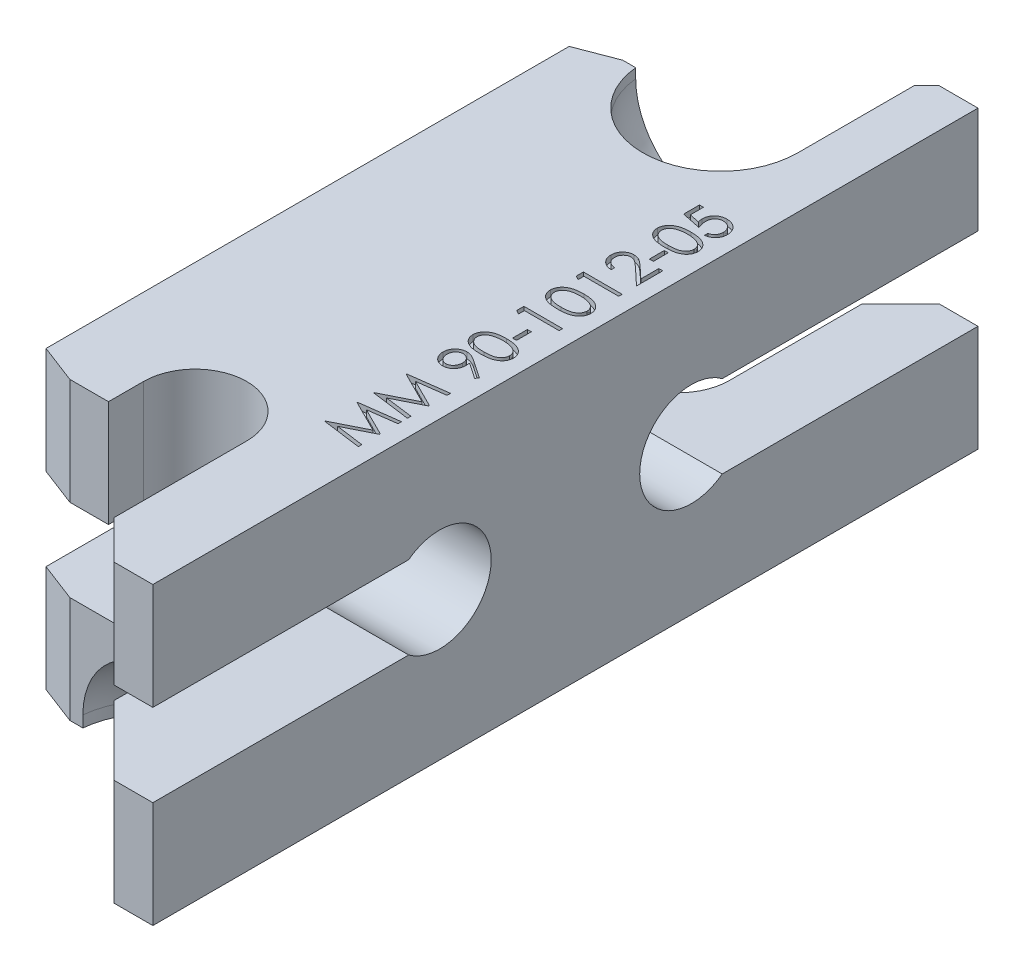
SolidWorks part; units mm, degrees
material "Acero M2"
ref_plane "Alzado" through (0, 0, 0) normal (0, 0, 1) x (1, 0, 0)
ref_plane "Planta" through (0, 0, 0) normal (0, 1, 0) x (1, 0, 0)
ref_plane "Vista lateral" through (0, 0, 0) normal (1, 0, 0) x (0, 0, -1)
sketch "Croquis1" plane through (0, 0, 0) normal (0, 1, 0) x (1, 0, 0)
  line L1 (15.875, -50.8) -> (0, -50.8)
  line L2 (15.875, -50.8) -> (15.875, 0)
  line L3 (15.875, 0) -> (0, 0)
  line L4 (0, -50.8) -> (0, 0)
  line L5 (7.9375, 0) -> (7.9375, -50.8) construction
  line L6 (15.875, -25.4) -> (0, -25.4) construction
  point P380 (7.9375, -25.4)
  dimension "D1" = 15.875
  dimension "D2" = 50.8
extrude "Saliente-Extruir1" add sketch "Croquis1" along normal blind 18.1864
sketch "Croquis2" plane through (15.875, 0, 0) normal (1, 0, 0) x (0, 0, -1)
  line L0 (-50.8, 9.0932) -> (-33.147, 9.0932) construction
  line L1 (-50.8, 18.1864) -> (-50.8, 0) construction
  line L2 (-33.147, 9.0932) -> (-17.653, 9.0932) construction
  circle A0 centre (-33.147, 9.0932) radius 3.175
  circle A1 centre (-17.653, 9.0932) radius 3.175
  dimension "D1" = 6.35
  dimension "D2" = 33.147
  dimension "D3" = 15.494
extrude "Cortar-Extruir1" cut sketch "Croquis2" against normal through all
sketch "Croquis3" plane through (15.875, 0, 0) normal (1, 0, 0) x (0, 0, -1)
  line L0 (-33.147, 9.0932) -> (-50.8, 9.0932) construction
  line L1 (-50.8, 18.1864) -> (-50.8, 0) construction
  line L2 (-33.147, 6.5532) -> (-50.8, 6.5532)
  line L3 (-33.147, 11.6332) -> (-50.8, 11.6332)
  line L4 (-17.653, 9.0932) -> (0, 9.0932) construction
  line L5 (0, 18.1864) -> (0, 0) construction
  line L6 (-17.653, 11.6332) -> (0, 11.6332)
  line L7 (-17.653, 6.5532) -> (0, 6.5532)
  arc A0 (-33.147, 6.5532) -> (-33.147, 11.6332) centre (-33.147, 9.0932) ccw
  arc A1 (-50.8, 11.6332) -> (-50.8, 6.5532) centre (-50.8, 9.0932) ccw
  arc A2 (-17.653, 11.6332) -> (-17.653, 6.5532) centre (-17.653, 9.0932) ccw
  arc A3 (0, 6.5532) -> (0, 11.6332) centre (0, 9.0932) ccw
  point P5 (-41.9735, 9.0932)
  point P10 (-8.8265, 9.0932)
  dimension "D1" = 5.08
extrude "Cortar-Extruir2" cut sketch "Croquis3" against normal through all
sketch "Croquis4" plane through (0, 0, 0) normal (0, -1, 0) x (1, 0, 0)
  line L0 (15.875, 50.8) -> (15.875, 0) construction
  line L1 (0, 50.8) -> (9.2329, 50.8)
  line L2 (0, 50.8) -> (0, 42.418)
  line L3 (0, 42.418) -> (9.2329, 42.418)
  line L4 (9.2329, 50.8) -> (9.2329, 42.418)
  line L5 (4.6165, 42.418) -> (4.6165, 50.8) construction
  line L6 (0, 46.609) -> (9.2329, 46.609) construction
  line L7 (0, 0) -> (9.2329, 0)
  line L8 (0, 0) -> (0, 8.382)
  line L9 (0, 8.382) -> (9.2329, 8.382)
  line L10 (9.2329, 0) -> (9.2329, 8.382)
  line L11 (4.6165, 8.382) -> (4.6165, 0) construction
  line L12 (0, 4.191) -> (9.2329, 4.191) construction
  point P124 (4.6165, 4.191)
  point P164 (4.6165, 46.609)
  dimension "D1" = 34.036
  dimension "D2" = 6.6421
extrude "Cortar-Extruir3" cut sketch "Croquis4" against normal through all
sketch "Croquis5" plane through (0, 0, 0) normal (0, -1, 0) x (1, 0, 0)
  line L0 (9.2329, 50.8) -> (13.4874, 50.8)
  line L1 (9.2329, 50.8) -> (15.875, 50.8) construction
  line L2 (13.4874, 50.8) -> (9.2329, 46.5455)
  line L3 (9.2329, 42.418) -> (9.2329, 50.8) construction
  line L4 (9.2329, 46.5455) -> (9.2329, 50.8)
  line L5 (15.875, 50.8) -> (15.875, 0) construction
  line L6 (0, 25.4) -> (15.875, 25.4) construction
  line L7 (0, 8.382) -> (0, 42.418) construction
  line L8 (9.2329, 4.2545) -> (9.2329, 0)
  line L9 (13.4874, 0) -> (9.2329, 4.2545)
  line L10 (9.2329, 0) -> (13.4874, 0)
  dimension "D1" = 45
  dimension "D2" = 2.3876
extrude "Cortar-Extruir4" cut sketch "Croquis5" against normal through all
chamfer "Chaflán1" distance 0.9144 angle 20 4 edges at (0, 14.9098, 8.382) (0, 3.2766, 8.382) (0, 14.9098, 42.418) (0, 3.2766, 42.418) first distance on face at (4.6165, 14.9098, 8.382) first distance on face at (4.6165, 3.2766, 8.382) first distance on face at (4.6165, 14.9098, 42.418) first distance on face at (4.6165, 3.2766, 42.418)
sketch "Croquis6" plane through (0, 0, 0) normal (0, -1, 0) x (1, 0, 0)
  line L0 (7.9375, 50.8) -> (7.9375, 42.8752) construction
  line L1 (12.7127, 50.8) -> (12.7127, 42.8752)
  line L2 (3.1623, 50.8) -> (3.1623, 42.8752)
  line L3 (0, 25.4) -> (15.875, 25.4) construction
  line L4 (0, 8.7148) -> (0, 42.0852) construction
  line L5 (15.875, 50.8) -> (15.875, 0) construction
  line L6 (7.9375, 25.4) -> (7.9375, 42.8752) construction
  line L7 (13.4874, 50.8) -> (15.875, 50.8) construction
  arc A0 (12.7127, 50.8) -> (3.1623, 50.8) centre (7.9375, 50.8) ccw
  arc A1 (3.1623, 42.8752) -> (12.7127, 42.8752) centre (7.9375, 42.8752) ccw
  point P2 (7.9375, 46.8376)
  dimension "D1" = 9.5504
  dimension "D2" = 7.9248
extrude "Cortar-Extruir5" cut sketch "Croquis6" against normal offset from surface (5.4585 mm away) 1.0947 up to face at (8.0772, 6.5532, 43.1463)
sketch "Croquis7" plane through (0, 18.1864, 0) normal (0, 1, 0) x (1, 0, 0)
  line L0 (0, -25.4) -> (15.875, -25.4) construction
  line L1 (0, -25.4) -> (15.875, -25.4) construction
  line L2 (12.7127, -50.8) -> (12.7127, -42.8752)
  line L3 (3.1623, -42.8752) -> (3.1623, -50.8)
  line L4 (12.7127, -50.8) -> (12.7127, -42.8752) construction
  line L5 (3.1623, -42.8752) -> (3.1623, -50.8) construction
  line L6 (3.1623, -7.9248) -> (3.1623, 0)
  line L7 (12.7127, 0) -> (12.7127, -7.9248)
  arc A0 (3.1623, 0) -> (12.7127, 0) centre (7.9375, 0) cw
  arc A1 (12.7127, -7.9248) -> (3.1623, -7.9248) centre (7.9375, -7.9248) cw
  arc A2 (12.7127, -42.8752) -> (3.1623, -42.8752) centre (7.9375, -42.8752) ccw
  arc A3 (3.1623, -50.8) -> (12.7127, -50.8) centre (7.9375, -50.8) ccw
  arc A4 (12.7127, -42.8752) -> (3.1623, -42.8752) centre (7.9375, -42.8752) ccw construction
  arc A5 (3.1623, -50.8) -> (12.7127, -50.8) centre (7.9375, -50.8) ccw construction
  dimension "D1" = 0
extrude "Cortar-Extruir6" cut sketch "Croquis7" against normal offset from surface (5.3543 mm away) 1.1989 up to face at (8.0772, 11.6332, 7.6537)
fillet "Redondeo1" radius 4.7625 4 edges at (12.7127, 5.4585, 46.4503) (8.1664, 12.8321, 12.6945) (8.1664, 5.4585, 38.1055) (12.7127, 12.8321, 4.3497)
sketch "Croquis8" plane through (0, 0, 0) normal (0, -1, 0) x (1, 0, 0)
  line L0 (7.9375, 50.8) -> (7.9375, 42.418) construction
  line L1 (9.2329, 50.8) -> (9.2329, 42.418)
  line L2 (6.6421, 50.8) -> (6.6421, 42.418)
  line L3 (7.9375, 50.8) -> (7.9375, 42.8752) construction
  line L4 (9.2329, 42.8752) -> (9.2329, 46.5455) construction
  line L5 (13.4874, 50.8) -> (15.875, 50.8) construction
  line L6 (0, 25.4) -> (15.875, 25.4) construction
  line L7 (0, 25.4) -> (15.875, 25.4) construction
  line L8 (7.9375, 0) -> (7.9375, 8.382) construction
  line L9 (9.2329, 0) -> (9.2329, 8.382)
  line L10 (6.6421, 0) -> (6.6421, 8.382)
  arc A0 (9.2329, 50.8) -> (6.6421, 50.8) centre (7.9375, 50.8) ccw
  arc A1 (6.6421, 42.418) -> (9.2329, 42.418) centre (7.9375, 42.418) ccw
  arc A2 (9.2329, 0) -> (6.6421, 0) centre (7.9375, 0) cw
  arc A3 (6.6421, 8.382) -> (9.2329, 8.382) centre (7.9375, 8.382) cw
  point P2 (7.9375, 46.609)
  point P19 (7.9375, 4.191)
  dimension "D1" = 8.382
extrude "Cortar-Extruir7" cut sketch "Croquis8" against normal through all
sketch "Croquis9" plane through (0, 0, 0) normal (0, -1, 0) x (1, 0, 0)
  line L0 (7.9375, 0) -> (7.9375, 10.541) construction
  line L1 (4.7625, 0) -> (4.7625, 10.541)
  line L2 (11.1125, 0) -> (11.1125, 10.541)
  line L3 (7.9375, 25.4) -> (7.9375, 42.8752) construction
  line L4 (15.875, 0) -> (13.4874, 0) construction
  arc A0 (4.7625, 0) -> (11.1125, 0) centre (7.9375, 0) ccw
  arc A1 (11.1125, 10.541) -> (4.7625, 10.541) centre (7.9375, 10.541) ccw
  point P2 (7.9375, 5.2705)
  dimension "D1" = 6.35
  dimension "D2" = 10.541
extrude "Cortar-Extruir8" cut sketch "Croquis9" against normal up to surface (6.5532 mm away) up to face at (7.9177, 6.5532, 7.8785)
sketch "Croquis10" plane through (0, 18.1864, 0) normal (0, 1, 0) x (1, 0, 0)
  line L0 (0, -25.4) -> (15.875, -25.4) construction
  line L1 (0, -25.4) -> (15.875, -25.4) construction
  line L2 (4.7625, 0) -> (4.7625, -10.541)
  line L3 (11.1125, -10.541) -> (11.1125, 0)
  line L4 (4.7625, 0) -> (4.7625, -10.541) construction
  line L5 (11.1125, -10.541) -> (11.1125, 0) construction
  line L6 (11.1125, -40.259) -> (11.1125, -50.8)
  line L7 (4.7625, -50.8) -> (4.7625, -40.259)
  arc A0 (11.1125, -50.8) -> (4.7625, -50.8) centre (7.9375, -50.8) cw
  arc A1 (4.7625, -40.259) -> (11.1125, -40.259) centre (7.9375, -40.259) cw
  arc A2 (4.7625, -10.541) -> (11.1125, -10.541) centre (7.9375, -10.541) ccw
  arc A3 (11.1125, 0) -> (4.7625, 0) centre (7.9375, 0) ccw
  arc A4 (4.7625, -10.541) -> (11.1125, -10.541) centre (7.9375, -10.541) ccw construction
  arc A5 (11.1125, 0) -> (4.7625, 0) centre (7.9375, 0) ccw construction
  dimension "D1" = 0
extrude "Cortar-Extruir9" cut sketch "Croquis10" against normal up to surface (6.5532 mm away) up to face at (7.9177, 11.6332, 42.9215)
sketch "Croquis11" plane through (0, 18.1864, 0) normal (0, 1, 0) x (1, 0, 0)
  line L0 (14.8472, -43.4561) -> (14.8472, -7.3439) construction
  line L1 (0, -25.4) -> (15.875, -25.4) construction
  text T0 "MM 90-1012-05" font "Century Gothic" height 2.3813
  point P4 (14.8472, -25.4)
extrude "Cortar-Extruir10" cut sketch "Croquis11" against normal blind 0.381
sketch "Croquis12" plane through (0, 18.1864, 0) normal (0, 1, 0) x (1, 0, 0)
  line L0 (2.382, -42.418) -> (-0.0056, -42.418)
  line L1 (0.9144, -42.418) -> (4.7625, -42.418) construction
  line L2 (-0.0056, -42.418) -> (0, -41.5036)
  line L3 (0, -8.7148) -> (0, -42.0852) construction
  line L4 (0, -41.5036) -> (2.382, -42.418)
  line L5 (0, -25.4) -> (15.875, -25.4) construction
  line L6 (15.875, -50.8) -> (15.875, 0) construction
  line L7 (0, -9.2964) -> (2.382, -8.382)
  line L8 (-0.0056, -8.382) -> (0, -9.2964)
  line L9 (2.382, -8.382) -> (-0.0056, -8.382)
  dimension "D1" = 0.9144
  dimension "D2" = 21
  dimension "D3" = 2.3876
extrude "Cortar-Extruir11" cut sketch "Croquis12" against normal through all
